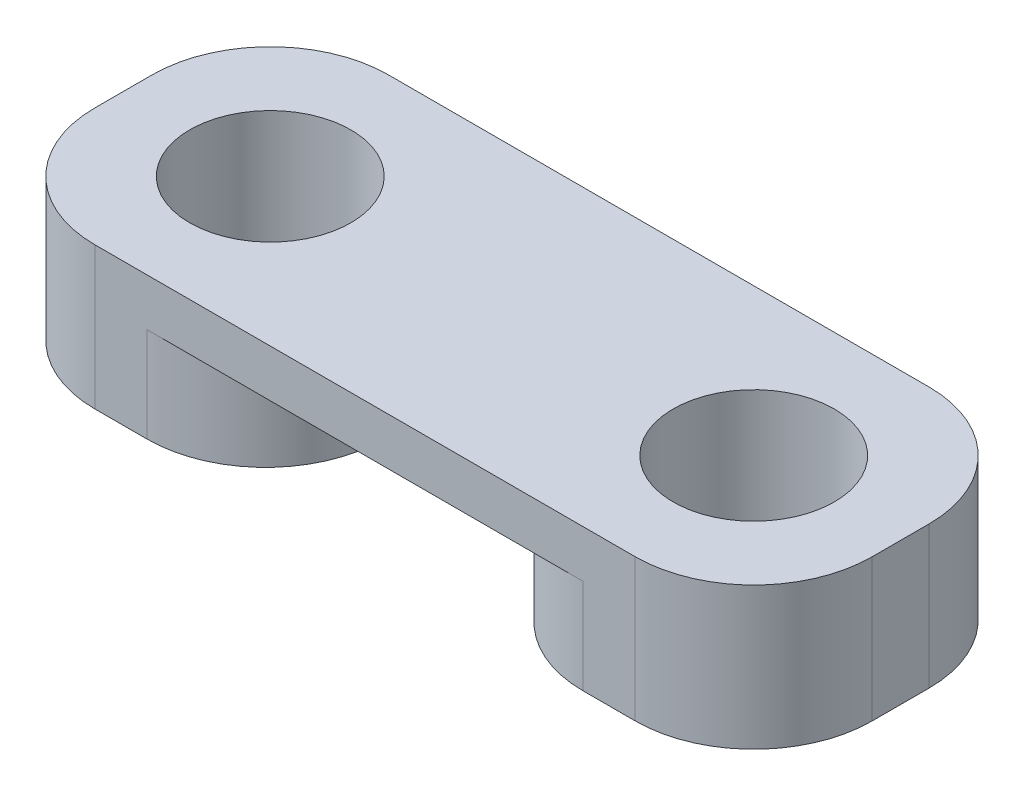
SolidWorks part; units mm, degrees
ref_plane "Front Plane" through (0, 0, 0) normal (0, 0, 1) x (1, 0, 0)
ref_plane "Top Plane" through (0, 0, 0) normal (0, 1, 0) x (1, 0, 0)
ref_plane "Right Plane" through (0, 0, 0) normal (1, 0, 0) x (0, 0, -1)
sketch "Sketch1" plane through (0, 0, 0) normal (0, 1, 0) x (1, 0, 0)
  line L0 (-8.199, 0) -> (8.199, 0)
  line L1 (8.199, 0) -> (8.199, 6.2)
  line L2 (8.199, 6.2) -> (-8.199, 6.2)
  line L3 (-8.199, 6.2) -> (-8.199, 0)
  line L4 (0, 0) -> (0, 9.4869) construction
  circle A0 centre (-5.099, 3.1) radius 1.7
  circle A1 centre (5.099, 3.1) radius 1.7
  point P3 (0, 0)
  point P12 (-8.199, 3.1)
  dimension "D1" = 3.4
  dimension "D2" = 6.2
  dimension "D3" = 5.099
  dimension "D4" = 16.398
extrude "Boss-Extrude1" add sketch "Sketch1" along normal blind 3
sketch "Sketch5" plane through (0, 0, 0) normal (0, 0, 1) x (1, 0, 0)
  line L0 (-2.099, 0) -> (-2.099, 2)
  line L1 (-8.199, 0) -> (8.199, 0) construction
  line L2 (-2.099, 2) -> (2.099, 2)
  line L3 (2.099, 2) -> (2.099, 0)
  line L4 (-8.199, 3) -> (8.199, 3) construction
  line L8 (-2.099, 0) -> (2.099, 0)
  point P8 (0, 0)
  dimension "D1" = 1
  dimension "D2" = 4.198
extrude "Cut-Extrude4" cut sketch "Sketch5" against normal through all
fillet "Fillet2" radius 2.5 8 edges at (8.199, 1.5, -6.2) (8.199, 1.5, 0) (-8.199, 1.5, -6.2) (-8.199, 1.5, 0) (2.099, 1, 0) (2.099, 1, -6.2) (-2.099, 1, -6.2) (-2.099, 1, 0)
equation "\"D3@Sketch1\"=10.198039/2"
